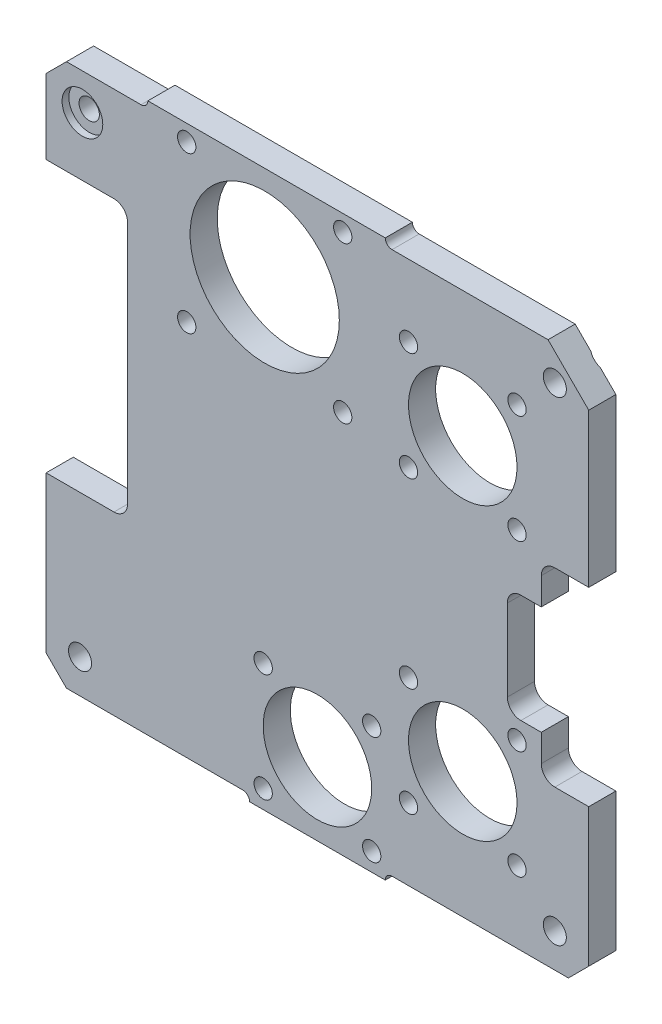
SolidWorks part; units mm, degrees
ref_plane "Спереди" through (0, 0, 0) normal (0, 0, 1) x (1, 0, 0)
ref_plane "Сверху" through (0, 0, 0) normal (0, 1, 0) x (1, 0, 0)
ref_plane "Справа" through (0, 0, 0) normal (1, 0, 0) x (0, 0, -1)
sketch "Эскиз1" plane through (0, 0, 0) normal (0, 0, 1) x (1, 0, 0)
  line L0 (-12.0121, -43.9087) -> (-29.1082, 15.7127) construction
  line L4 (27.9879, -32.9087) -> (27.9879, -9.9087)
  line L5 (-49.0121, -83.9087) -> (24.9879, -83.9087)
  line L6 (27.9879, -32.9087) -> (27.9879, -9.9087)
  line L7 (21.9879, -3.9087) -> (-49.0121, -3.9087)
  line L8 (25.9879, -52.9087) -> (25.9879, -34.9087)
  line L9 (-49.0121, -83.9087) -> (24.9879, -83.9087)
  line L10 (25.9879, -52.9087) -> (25.9879, -34.9087)
  line L11 (21.9879, -3.9087) -> (-49.0121, -3.9087)
  line L32 (27.9879, -80.9087) -> (27.9879, -54.9087)
  line L33 (27.9879, -80.9087) -> (27.9879, -54.9087)
  line L34 (-52.0121, -54.9087) -> (-52.0121, -80.9087)
  line L35 (-52.0121, -54.9087) -> (-52.0121, -80.9087)
  line L36 (-50.0121, -34.9087) -> (-50.0121, -52.9087)
  line L37 (-50.0121, -34.9087) -> (-50.0121, -52.9087)
  line L38 (-52.0121, -6.9087) -> (-52.0121, -32.9087)
  line L39 (-52.0121, -6.9087) -> (-52.0121, -32.9087)
  line L44 (-12.0121, -43.9087) -> (26.4879, -82.4087) construction
  line L45 (-12.0121, -43.9087) -> (25.9879, -43.9087) construction
  line L46 (-12.0121, -43.9087) -> (-12.0121, 5.5902) construction
  line L47 (-12.0121, -43.9087) -> (-12.0121, -109.9956) construction
  line L48 (-12.0121, -43.9087) -> (27.4154, -4.4812) construction
  line L56 (-52.0121, -80.9087) -> (-49.0121, -83.9087)
  line L57 (-52.0121, -80.9087) -> (-49.0121, -83.9087)
  line L66 (26.9879, -8.9087) -> (21.9879, -3.9087)
  line L74 (-49.0121, -3.9087) -> (-52.0121, -6.9087)
  line L75 (-49.0121, -3.9087) -> (-52.0121, -6.9087)
  line L78 (24.9879, -83.9087) -> (27.9879, -80.9087)
  line L79 (24.9879, -83.9087) -> (27.9879, -80.9087)
  line L104 (27.9879, -9.9087) -> (26.9879, -8.9087)
  line L105 (27.9879, -9.9087) -> (21.9879, -3.9087)
  circle A1 centre (-19.785, -16.8011) radius 11
  circle A3 centre (9.4133, -22.4834) radius 8
  circle A5 centre (-12.0121, -74.2087) radius 8
  circle A7 centre (9.4133, -65.334) radius 8
  arc A16 (27.9879, -32.9087) -> (25.9879, -34.9087) centre (27.9879, -34.9087) ccw
  arc A17 (27.9879, -32.9087) -> (25.9879, -34.9087) centre (27.9879, -34.9087) ccw
  arc A18 (25.9879, -52.9087) -> (27.9879, -54.9087) centre (27.9879, -52.9087) ccw
  arc A19 (25.9879, -52.9087) -> (27.9879, -54.9087) centre (27.9879, -52.9087) ccw
  arc A20 (-52.0121, -54.9087) -> (-50.0121, -52.9087) centre (-52.0121, -52.9087) ccw
  arc A21 (-52.0121, -54.9087) -> (-50.0121, -52.9087) centre (-52.0121, -52.9087) ccw
  arc A22 (-50.0121, -34.9087) -> (-52.0121, -32.9087) centre (-52.0121, -34.9087) ccw
  arc A23 (-50.0121, -34.9087) -> (-52.0121, -32.9087) centre (-52.0121, -34.9087) ccw
  circle A27 centre (-12.0121, -43.9087) radius 30.3 construction
  circle A28 centre (-12.0121, -43.9087) radius 28.2 construction
  arc A41 (26.9879, -8.9087) -> (26.9879, -8.9087) centre (22.9879, -8.9087) ccw
  dimension "D2" = 16
  dimension "D3" = 60.6
  dimension "D4" = 22
  dimension "D5" = 16
  dimension "D7" = 16
  dimension "D8" = 56.4
  dimension "D6" = 45
  dimension "D9" = 16
  dimension "D1" = 0
extrude "Вытянуть1" add sketch "Эскиз1" along normal blind 4
sketch "Эскиз2" plane through (0, 0, 4) normal (0, 0, 1) x (1, 0, 0)
  line L0 (35.4031, -43.9087) -> (-59.4272, -43.9087) construction
  line L1 (-49.0121, -83.9087) -> (24.9879, -83.9087) construction
  line L3 (-12.0121, -43.9087) -> (-73.7316, 17.8109) construction
  line L4 (27.9879, -80.9087) -> (27.9879, -54.9087) construction
  line L6 (-49.0121, -83.9087) -> (24.9879, -83.9087) construction
  circle A1 centre (-12.0121, -43.9087) radius 49 construction
  circle A2 centre (-46.6603, -9.2605) radius 1.5
  dimension "D1" = 3
  dimension "D2" = 98
  dimension "D5" = 40
  dimension "D3" = 45
  dimension "D4" = 40
extrude "Вырез-Вытянуть1" cut sketch "Эскиз2" against normal blind 5
hole_wizard "Отверстие обработанное метчиком M2x0.41" [suppressed] positions "Трехмерный эскиз1" profile "Эскиз3" tap size "M2x0.4" standard "Ansi (метрические)"
sketch3d "Трехмерный эскиз1"
  point P0 (20.5728, -76.5349, 2)
  point P2 (20.5728, -16.5349, 2)
  point P4 (10.5728, -6.5349, 2)
  point P5 (-49.4272, -6.5349, 2)
  point P7 (-59.4272, -16.5349, 2)
  point P9 (-59.4272, -76.5349, 2)
  point P11 (-49.4272, -86.5349, 2)
  point P13 (10.5728, -86.5349, 2)
  dimension "D1" = 2
  dimension "D2" = 2
  dimension "D3" = 10
  dimension "D4" = 10
  dimension "D5" = 10
  dimension "D6" = 2
  dimension "D7" = 2
  dimension "D8" = 10
  dimension "D9" = 2
  dimension "D10" = 10
  dimension "D11" = 10
  dimension "D12" = 2
  dimension "D13" = 2
  dimension "D14" = 10
  dimension "D15" = 2
  dimension "D16" = 10
sketch "Эскиз3" plane through (20.5728, -76.5349, 2) normal (0, 1, 0) x (0, 0, -1)
  line L0 (0, 0) -> (0, 6.4807)
  line L1 (0, 6.4807) -> (0.8, 6)
  line L2 (0.8, 6) -> (0.8, 0)
  line L5 (0.8, 0) -> (0, 0)
  line L10 (0, 6.4807) -> (-0.8, 6) construction
  line L11 (0, -6.35) -> (0, 107.95) construction
  dimension "Диаметр сверла" = 1.6
  dimension "Глубина сверла" = 6
  dimension "Угол заточки сверла" = 118
cosmetic thread "Отверстие резьбы1" [suppressed] parameters "D1"=4, "D2"=2
cosmetic thread "Отверстие резьбы2" [suppressed] parameters "D1"=4, "D2"=2
cosmetic thread "Отверстие резьбы3" [suppressed] parameters "D1"=4, "D2"=2
cosmetic thread "Отверстие резьбы4" [suppressed] parameters "D1"=4, "D2"=2
cosmetic thread "Отверстие резьбы5" [suppressed] parameters "D1"=4, "D2"=2
cosmetic thread "Отверстие резьбы6" [suppressed] parameters "D1"=4, "D2"=2
cosmetic thread "Отверстие резьбы7" [suppressed] parameters "D1"=4, "D2"=2
cosmetic thread "Отверстие резьбы8" [suppressed] parameters "D1"=4, "D2"=2
hole_wizard "Диаметр отверстия Ø2.7 (2.7)1" positions "Трехмерный эскиз2" profile "Эскиз4" hole size "Ø2.7" standard "Ansi (метрические)"
sketch3d "Трехмерный эскиз2"
  line L0 (-19.785, -16.8011, 4) -> (-31.9628, -16.8011, 4) construction
  line L1 (-19.785, -16.8011, 4) -> (-19.785, -16.8011, 0) construction
  line L3 (-19.785, -16.8011, 4) -> (-19.785, -2.4884, 4) construction
  line L5 (9.4133, -22.4834, 4) -> (13.8012, -22.4834, 4) construction
  line L6 (9.4133, -22.4834, 4) -> (9.4133, -22.4834, 0) construction
  line L8 (9.4133, -22.4834, 4) -> (9.4133, -79.94, 4) construction
  line L10 (-12.0121, -74.2087, 4) -> (-12.0121, -62.4841, 4) construction
  line L11 (-12.0121, -74.2087, 4) -> (-12.0121, -74.2087, 0) construction
  line L13 (-12.0121, -74.2087, 4) -> (-33.3357, -74.2087, 4) construction
  line L15 (9.4133, -65.334, 4) -> (18.3318, -65.334, 4) construction
  line L16 (9.4133, -65.334, 4) -> (9.4133, -65.334, 0) construction
  point P0 (-8.285, -5.3011, 4)
  point P2 (-8.285, -28.3011, 4)
  point P4 (-31.285, -28.3011, 4)
  point P6 (-31.285, -5.3011, 4)
  point P22 (17.4133, -14.4834, 4)
  point P24 (17.4133, -30.4834, 4)
  point P26 (1.4133, -30.4834, 4)
  point P28 (1.4133, -14.4834, 4)
  point P30 (17.4133, -57.334, 4)
  point P32 (17.4133, -73.334, 4)
  point P34 (1.4133, -73.334, 4)
  point P36 (1.4133, -57.334, 4)
  point P38 (-4.0121, -66.2087, 4)
  point P40 (-4.0121, -82.2087, 4)
  point P42 (-20.0121, -66.2087, 4)
  point P44 (-20.0121, -82.2087, 4)
  dimension "D1" = 23
  dimension "D2" = 23
  dimension "D3" = 23
  dimension "D4" = 11.5
  dimension "D5" = 11.5
  dimension "D6" = 11.5
  dimension "D7" = 11.5
  dimension "D8" = 11.5
  dimension "D9" = 8
  dimension "D10" = 16
  dimension "D11" = 8
  dimension "D12" = 16
  dimension "D13" = 8
  dimension "D14" = 16
  dimension "D15" = 16
  dimension "D16" = 8
  dimension "D17" = 8
  dimension "D18" = 8
  dimension "D19" = 16
  dimension "D20" = 16
  dimension "D21" = 8
  dimension "D22" = 8
  dimension "D23" = 16
  dimension "D24" = 16
  dimension "D25" = 16
  dimension "D26" = 8
  dimension "D27" = 8
  dimension "D28" = 16
  dimension "D29" = 8
  dimension "D30" = 8
  dimension "D31" = 8
  dimension "D32" = 8
sketch "Эскиз4" plane through (-8.285, -5.3011, 4) normal (1, 0, 0) x (0, -1, 0)
  line L0 (0, 0) -> (0, 8.7794)
  line L1 (0, 8.7794) -> (1.35, 8)
  line L2 (1.35, 8) -> (1.35, 0)
  line L5 (1.35, 0) -> (0, 0)
  line L10 (0, 8.7794) -> (-1.35, 8) construction
  line L11 (0, -6.35) -> (0, 107.95) construction
  dimension "Диаметр отверстия" = 2.7
  dimension "Глубина отверстия" = 8
  dimension "Угол заточки сверла" = 120
sketch "Эскиз5" plane through (0, -3.9087, 0) normal (0, 1, 0) x (1, 0, 0)
  line L0 (21.9879, -4) -> (-49.0121, -4) construction
  line L1 (-2.0121, -4) -> (-37.0121, -4)
  line L2 (-2.0121, -4) -> (-2.0121, 0)
  line L3 (-2.0121, 0) -> (-37.0121, 0)
  line L4 (-37.0121, -4) -> (-37.0121, 0)
  line L5 (21.9879, 0) -> (-49.0121, 0) construction
  line L8 (-52.0121, -4) -> (-52.0121, 0) construction
  dimension "D1" = 35
  dimension "D2" = 15
extrude "Вытянуть2" add sketch "Эскиз5" along normal blind 1
fillet "Скругление1" radius 1 2 edges
sketch "Эскиз6" plane through (0, -83.9087, 0) normal (0, -1, 0) x (1, 0, 0)
  line L0 (-49.0121, 4) -> (24.9879, 4) construction
  line L1 (-2.0121, 4) -> (-22.0121, 4)
  line L2 (-2.0121, 4) -> (-2.0121, 0)
  line L3 (-2.0121, 0) -> (-22.0121, 0)
  line L4 (-22.0121, 4) -> (-22.0121, 0)
  line L5 (-49.0121, 0) -> (24.9879, 0) construction
  line L7 (27.9879, 4) -> (27.9879, 0) construction
  dimension "D1" = 30
  dimension "D2" = 20
extrude "Вытянуть3" add sketch "Эскиз6" along normal blind 1
fillet "Скругление2" radius 1 2 edges
sketch "Эскиз7" plane through (0, 0, 0) normal (0, 0, -1) x (-1, 0, 0)
  line L0 (-27.9879, -32.9087) -> (-27.9879, -9.9087) construction
  line L1 (52.0121, -17.9087) -> (42.0121, -17.9087)
  line L2 (52.0121, -17.9087) -> (52.0121, -57.9087)
  line L3 (52.0121, -57.9087) -> (42.0121, -57.9087)
  line L4 (40.0121, -19.9087) -> (40.0121, -55.9087)
  line L5 (38.0121, -3.9087) -> (49.0121, -3.9087) construction
  line L6 (-20.9879, -54.5349) -> (-20.9879, -58.5349)
  line L7 (-27.9879, -32.5349) -> (-22.9879, -32.5349)
  line L8 (-20.9879, -34.5349) -> (-20.9879, -38.5349)
  line L9 (-22.9879, -60.5349) -> (-27.9879, -60.5349)
  line L10 (61.4272, -46.5349) -> (-37.8567, -46.5349) construction
  line L11 (-20.9879, -54.5349) -> (-17.9879, -54.5349)
  line L12 (-27.9879, -60.5349) -> (-27.9879, -32.5349)
  line L13 (-20.9879, -38.5349) -> (-17.9879, -38.5349)
  line L14 (52.0121, -6.9087) -> (52.0121, -32.9087) construction
  line L15 (-15.9879, -40.5349) -> (-15.9879, -52.5349)
  arc A0 (42.0121, -57.9087) -> (40.0121, -55.9087) centre (42.0121, -55.9087) cw
  arc A1 (40.0121, -19.9087) -> (42.0121, -17.9087) centre (42.0121, -19.9087) cw
  arc A2 (-20.9879, -58.5349) -> (-22.9879, -60.5349) centre (-22.9879, -58.5349) cw
  arc A3 (-20.9879, -34.5349) -> (-22.9879, -32.5349) centre (-22.9879, -34.5349) ccw
  arc A4 (-17.9879, -38.5349) -> (-15.9879, -40.5349) centre (-17.9879, -40.5349) cw
  arc A5 (-15.9879, -52.5349) -> (-17.9879, -54.5349) centre (-17.9879, -52.5349) cw
  dimension "D4" = 2
  dimension "D9" = 2
  dimension "D13" = 2
  dimension "D1" = 14
  dimension "D2" = 12
  dimension "D3" = 40
  dimension "D5" = 11.3738
  dimension "D6" = 14
  dimension "D7" = 7
  dimension "D8" = 28
  dimension "D10" = 16
  dimension "D11" = 8
  dimension "D12" = 12
extrude "Вытянуть4" cut sketch "Эскиз7" against normal blind 10
sketch "Эскиз8" plane through (0, 0, 4) normal (0, 0, 1) x (1, 0, 0)
  circle A0 centre (-46.6603, -9.2605) radius 3
  dimension "D1" = 6
extrude "Вытянуть5" cut sketch "Эскиз8" against normal blind 1
hole_wizard "Зенковка для винта с потайной головкой M31" positions "Трехмерный эскиз3" profile "Эскиз9" countersink size "M3" standard "ISO" end condition through all
sketch3d "Трехмерный эскиз3"
  line L0 (-1.0121, -83.9087, 0) -> (24.9879, -83.9087, 0) construction
  line L1 (27.9879, -80.9087, 0) -> (27.9879, -60.5349, 0) construction
  line L2 (27.9879, -32.5349, 0) -> (27.9879, -9.9087, 0) construction
  line L3 (21.9879, -3.9087, 0) -> (-1.0121, -3.9087, 0) construction
  line L4 (-49.0121, -83.9087, 0) -> (-23.0121, -83.9087, 0) construction
  line L5 (-52.0121, -57.9087, 0) -> (-52.0121, -80.9087, 0) construction
  point P0 (22.9879, -78.9087, 0)
  point P2 (-47.0121, -78.9087, 0)
  point P4 (22.9879, -8.9087, 0)
  dimension "D1" = 5
  dimension "D2" = 5
  dimension "D3" = 5
  dimension "D4" = 5
  dimension "D5" = 5
  dimension "D6" = 5
sketch "Эскиз9" plane through (22.9879, -78.9087, 0) normal (1, 0, 0) x (0, 1, 0)
  line L0 (0, 0) -> (0, 4)
  line L1 (0, 4) -> (1.7, 4)
  line L2 (1.7, 4) -> (1.7, 1.3)
  line L3 (1.7, 1.3) -> (3, 0)
  line L5 (3, 0) -> (0, 0)
  line L6 (-1.7, 1.3) -> (-3, 0) construction
  line L11 (0, -6.35) -> (0, 107.95) construction
  dimension "Диаметр сквозного отверстия" = 3.4
  dimension "Глубина сквозного отверстия" = 4
  dimension "Диаметр передней зенковки" = 6
  dimension "Угол передней зенковки" = 90
sketch "Эскиз10" plane through (0, 0, 4) normal (0, 0, 1) x (1, 0, 0)
  circle A1 centre (15.5728, -81.5349) radius 1.7
  circle A3 centre (15.5728, -11.5349) radius 1.7
  circle A5 centre (-54.4272, -81.5349) radius 1.7
  circle A6 centre (15.5728, -81.5349) radius 4
  circle A7 centre (15.5728, -11.5349) radius 4
  circle A8 centre (-54.4272, -81.5349) radius 4
  dimension "D1" = 8
  dimension "D2" = 8
  dimension "D3" = 8
extrude "Вытянуть6" [suppressed] cut sketch "Эскиз10" against normal blind 2
